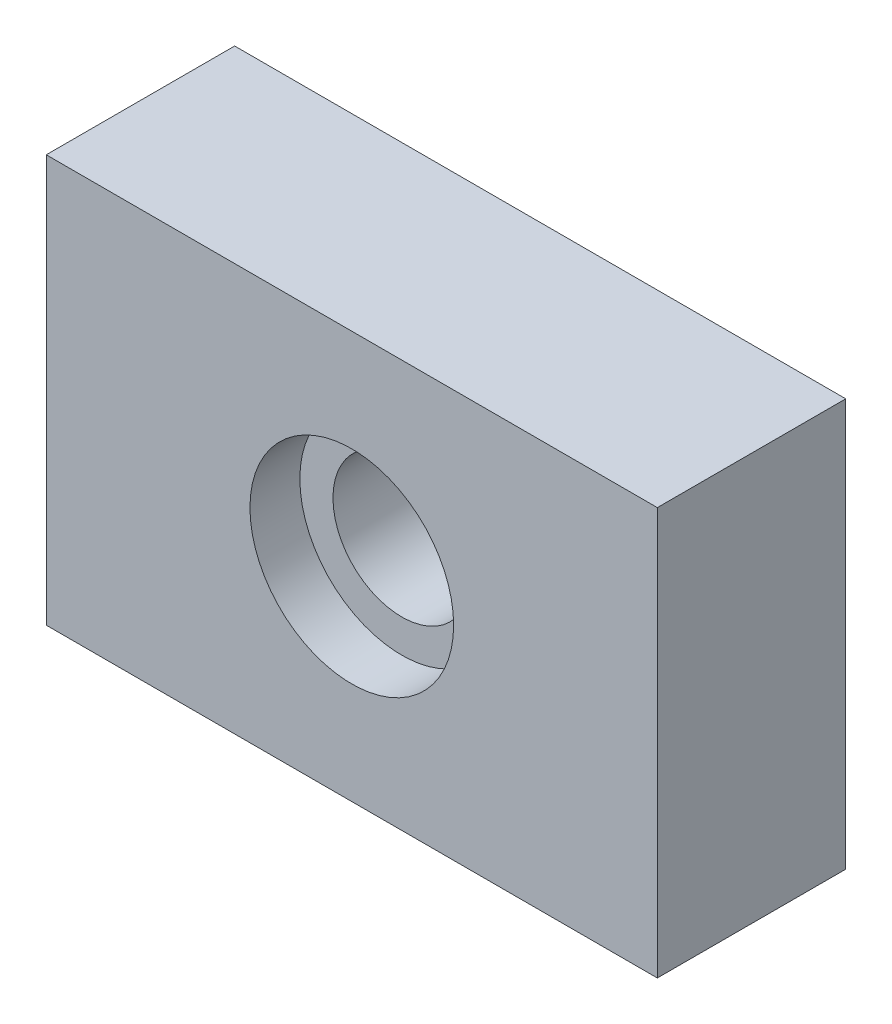
SolidWorks part; units mm, degrees
ref_plane "Front Plane" through (0, 0, 0) normal (0, 0, 1) x (1, 0, 0)
ref_plane "Top Plane" through (0, 0, 0) normal (0, 1, 0) x (1, 0, 0)
ref_plane "Right Plane" through (0, 0, 0) normal (1, 0, 0) x (0, 0, -1)
sketch "Sketch1" plane through (0, 0, 0) normal (0, 0, 1) x (1, 0, 0)
  line L1 (0, 0) -> (152.4, 0)
  line L2 (0, 0) -> (0, 101.6)
  line L3 (0, 101.6) -> (152.4, 101.6)
  line L4 (152.4, 0) -> (152.4, 101.6)
  dimension "D1" = 152.4
  dimension "D2" = 101.6
extrude "Boss-Extrude1" add sketch "Sketch1" along normal blind 46.99
sketch "Sketch2" plane through (0, 0, 0) normal (0, 0, -1) x (-1, 0, 0)
  line L0 (0, 50.8) -> (-152.4, 50.8) construction
  line L1 (0, 101.6) -> (0, 0) construction
  line L2 (-152.4, 0) -> (-152.4, 101.6) construction
  line L4 (-152.4, 101.6) -> (0, 101.6) construction
  line L5 (-76.2, 101.6) -> (-76.2, 0) construction
  line L6 (0, 0) -> (-152.4, 0) construction
  circle A0 centre (-76.2, 50.8) radius 25.4
  circle A1 centre (-76.2, 50.8) radius 17.145
  dimension "D1" = 50.8
  dimension "D2" = 34.29
extrude "Cut-Extrude1" cut sketch "Sketch2" against normal through all contours A1
extrude "Cut-Extrude3" cut sketch "Sketch2<2>" against normal blind 12.446
sketch "Sketch2<2>" plane through (0, 0, 0) normal (0, 0, -1) x (-1, 0, 0) same geometry as "Sketch2"
ref_plane "Plane2" through (0, 0, 23.495) normal (0, 0, -1) x (-1, 0, 0)
mirror "Mirror2" about plane through (0, 0, 23.495) normal (0, 0, -1) of "Cut-Extrude3"
hole_wizard "Tap Drill for 1/2-13 Tap1" positions "Sketch4" profile "Sketch5" hole size "1/2-13" standard "ANSI Inch"
sketch "Sketch4" plane through (0, 0, 0) normal (0, -1, 0) x (-1, 0, 0)
  line L0 (55.88, -23.495) -> (-55.88, -23.495) construction
  line L2 (-76.2, -46.99) -> (-76.2, 0) construction
  line L3 (0, -46.99) -> (-152.4, -46.99) construction
  line L4 (0, 0) -> (-152.4, 0) construction
  point P0 (-95.25, -23.495)
  point P4 (-57.15, -23.495)
  dimension "D1" = 19.05
  dimension "D2" = 19.05
sketch "Sketch5" plane through (95.25, 0, 23.495) normal (1, 0, 0) x (0, 0, -1)
  line L0 (0, 0) -> (0, 15.9195)
  line L1 (0, 15.9195) -> (5.3581, 12.7)
  line L2 (5.3581, 12.7) -> (5.3581, 0)
  line L5 (5.3581, 0) -> (0, 0)
  line L10 (0, 15.9195) -> (-5.3581, 12.7) construction
  line L11 (0, -6.35) -> (0, 107.95) construction
  dimension "Hole Dia." = 10.7163
  dimension "Hole Depth" = 12.7
  dimension "Drill Angle" = 118
equation "\"through_diamiter\"= 1.35"
equation "\"D2@Sketch2\"= \"through_diamiter\""
equation "\"bearing depth\"= 0.5"
equation "\"hole spacing\"= 0.75"
equation "\"D2@Sketch4\"=\"hole spacing\""
equation "\"D1@Sketch4\"=\"hole spacing\""
